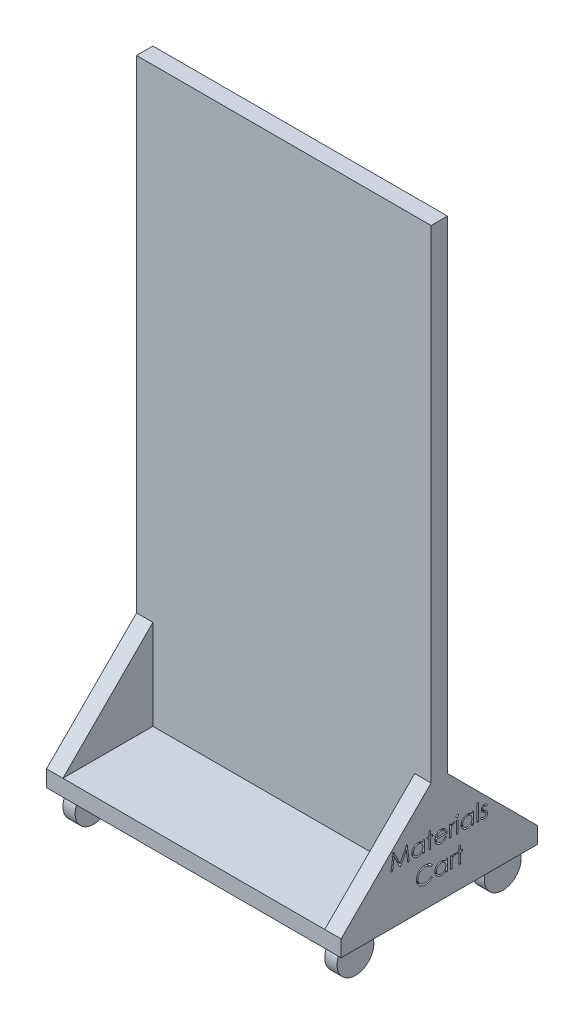
SolidWorks part; units mm, degrees
ref_plane "Front Plane" through (0, 0, 0) normal (0, 0, 1) x (1, 0, 0)
ref_plane "Top Plane" through (0, 0, 0) normal (0, 1, 0) x (1, 0, 0)
ref_plane "Right Plane" through (0, 0, 0) normal (1, 0, 0) x (0, 0, -1)
sketch "Sketch1" plane through (0, 0, 0) normal (0, 1, 0) x (1, 0, 0)
  line L1 (-457.2, -304.8) -> (457.2, -304.8)
  line L2 (-457.2, -304.8) -> (-457.2, 304.8)
  line L3 (-457.2, 304.8) -> (457.2, 304.8)
  line L4 (457.2, -304.8) -> (457.2, 304.8)
  line L5 (-457.2, -304.8) -> (457.2, 304.8) construction
  line L6 (-457.2, 304.8) -> (457.2, -304.8) construction
  point P0 (0, 0)
  dimension "D1" = 609.6
  dimension "D2" = 914.4
extrude "Boss-Extrude1" add sketch "Sketch1" along normal blind 50.8
sketch "Sketch3" plane through (0, 0, 0) normal (0, 0, 1) x (1, 0, 0)
  line L0 (457.2, 50.8) -> (457.2, 0) construction
  line L1 (-457.2, 0) -> (457.2, 0)
  line L2 (-457.2, 0) -> (-457.2, 1828.8)
  line L3 (-457.2, 1828.8) -> (457.2, 1828.8)
  line L4 (457.2, 0) -> (457.2, 1828.8)
  line L5 (-457.2, 50.8) -> (-457.2, 0) construction
  line L6 (-457.2, 0) -> (457.2, 0) construction
  dimension "D1" = 1828.8
extrude "Boss-Extrude2" add sketch "Sketch3" along normal mid plane 50.8
sketch "Sketch4" plane through (457.2, 0, 0) normal (1, 0, 0) x (0, 0, -1)
  line L0 (304.8, 0) -> (304.8, 50.8)
  line L1 (304.8, 50.8) -> (25.4, 330.2)
  line L2 (25.4, 50.8) -> (25.4, 1828.8) construction
  line L3 (25.4, 330.2) -> (-25.4, 330.2)
  line L4 (-25.4, 50.8) -> (-25.4, 1828.8) construction
  line L5 (-25.4, 330.2) -> (-304.8, 50.8)
  line L6 (-304.8, 50.8) -> (-304.8, 0)
  line L7 (-304.8, 0) -> (304.8, 0)
  line L8 (25.4, 50.8) -> (304.8, 50.8) construction
  dimension "D1" = 45
extrude "Boss-Extrude3" add sketch "Sketch4" against normal blind 50.8
mirror "Mirror1" about plane through (0, 0, 0) normal (1, 0, 0) of "Boss-Extrude3"
ref_plane "Plane1" through (406.4, 0, 0) normal (1, 0, 0) x (0, 0, -1)
sketch "Sketch5" plane through (406.4, 0, 0) normal (1, 0, 0) x (0, 0, -1)
  line L0 (-228.6, -44.45) -> (228.6, -44.45) construction
  line L1 (-304.8, 0) -> (304.8, 0) construction
  line L2 (304.8, 50.8) -> (304.8, 0) construction
  circle A0 centre (-228.6, -44.45) radius 57.15
  circle A1 centre (228.6, -44.45) radius 57.15
  point P4 (0, -44.45)
  dimension "D1" = 114.3
  dimension "D2" = 101.6
  dimension "D3" = 76.2
extrude "Boss-Extrude4" add sketch "Sketch5" along normal mid plane 38.1
mirror "Mirror2" about plane through (0, 0, 0) normal (1, 0, 0) of "Boss-Extrude4"
sketch "Sketch6" plane through (457.2, 0, 0) normal (1, 0, 0) x (0, 0, -1)
  line L0 (-203.2, 152.4) -> (203.2, 152.4) construction
  line L4 (-25.4, 330.2) -> (-304.8, 50.8) construction
  line L5 (304.8, 50.8) -> (25.4, 330.2) construction
  line L6 (-304.8, 0) -> (304.8, 0) construction
  text T0 "Materials\r\nCart" font "Century Gothic" height 50.8
  dimension "D1" = 152.4
extrude "Cut-Extrude1" cut sketch "Sketch6" against normal blind 12.7
